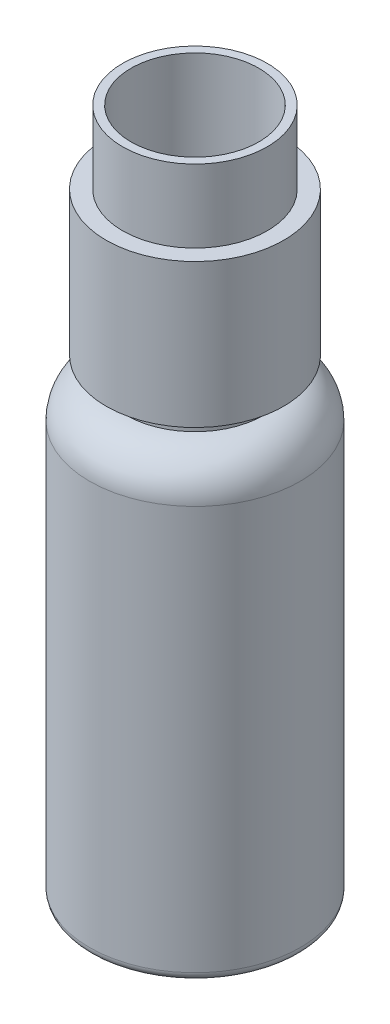
SolidWorks part; units mm, degrees
other "Markup1"
sketch "Sketch2" plane through (-11.875, 89.975, 11.875) normal (-0.9195, 0.3318, 0.2107) x (0.2261, 0.0082, 0.9741)
ref_plane "Front Plane" through (0, 0, 0) normal (0, 0, 1) x (1, 0, 0)
ref_plane "Top Plane" through (0, 0, 0) normal (0, 1, 0) x (1, 0, 0)
ref_plane "Right Plane" through (0, 0, 0) normal (1, 0, 0) x (0, 0, -1)
ref_axis "Axis1" through (0, -4.4988, 0) along (0, 1, 0)
sketch "Sketch1" plane through (0, 0, 0) normal (0, 0, 1) x (1, 0, 0)
  line L0 (9.75, 0) -> (10.875, 0)
  line L1 (11.875, 1) -> (11.875, 46.5)
  line L3 (0, -4.4988) -> (0, 94.4737) construction
  line L4 (8.75, 1) -> (8.75, 1.4096)
  line L5 (7.75, 2.4096) -> (0, 2.4096)
  line L6 (0, 65.8) -> (0, 2.4096)
  line L11 (0, 63.575) -> (0, 65.8)
  line L12 (7.5, 50.875) -> (7.75, 50.875)
  line L13 (7.75, 50.875) -> (7.75, 52.875)
  line L14 (7.75, 52.875) -> (10, 52.875)
  line L15 (10, 52.875) -> (10, 69.075)
  line L16 (10, 69.075) -> (8.15, 69.075)
  line L17 (8.15, 69.075) -> (8.15, 77.275)
  line L18 (8.15, 77.275) -> (7.2, 77.275)
  line L19 (7.2, 77.275) -> (7.2, 63.575)
  line L20 (0, 63.575) -> (7.2, 63.575)
  arc A0 (11.875, 46.5) -> (7.5, 50.875) centre (7.5, 46.5) ccw
  arc A1 (8.75, 1.4096) -> (7.75, 2.4096) centre (7.75, 1.4096) ccw
  arc A2 (9.75, 0) -> (8.75, 1) centre (9.75, 1) cw
  arc A3 (10.875, 0) -> (11.875, 1) centre (10.875, 1) ccw
  dimension "D1" = 1
  dimension "D2" = 1
  dimension "D3" = 7.75
  dimension "D4" = 8.15
  dimension "D5" = 11.875
  dimension "D6" = 2
  dimension "D7" = 16.2
  dimension "D8" = 10
  dimension "D9" = 8.2
  dimension "D10" = 13.7
  dimension "D11" = 7.2
  dimension "D12" = 45.5
revolve "Revolve1" add sketch "Sketch1" angle 360 about L6 region at (5.8457, 32.8031, 0)
